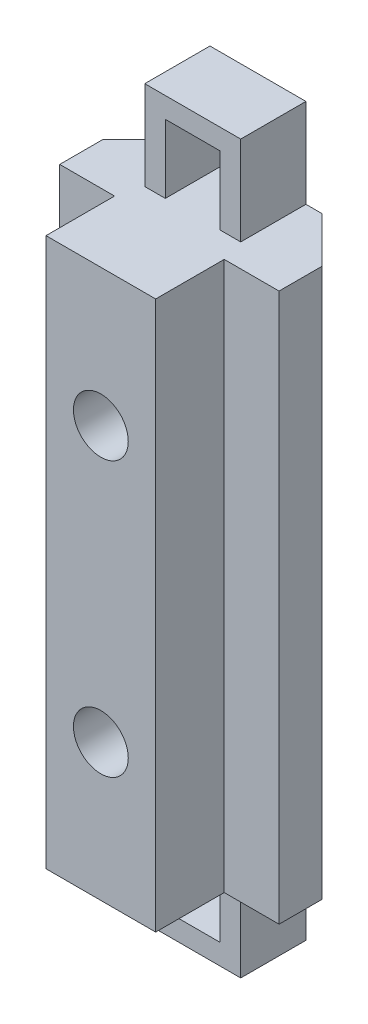
SolidWorks part; units mm, degrees
ref_plane "Front Plane" through (0, 0, 0) normal (0, 0, 1) x (1, 0, 0)
ref_plane "Top Plane" through (0, 0, 0) normal (0, 1, 0) x (1, 0, 0)
ref_plane "Right Plane" through (0, 0, 0) normal (1, 0, 0) x (0, 0, -1)
sketch "Sketch1" plane through (0, 0, 0) normal (0, 1, 0) x (1, 0, 0)
  line L0 (-4.2479, 4.7026) -> (8.7521, 4.7026)
  line L1 (8.7521, 4.7026) -> (8.7521, 1.7026)
  line L2 (-4.2479, 4.7026) -> (-4.2479, 1.7026)
  line L3 (-4.2479, 1.7026) -> (-2.5453, 0)
  line L4 (-44.2539, 0) -> (44.2539, 0) construction
  line L5 (8.7521, 1.7026) -> (7.0495, 0)
  line L6 (-2.5453, 0) -> (7.0495, 0)
  dimension "D1" = 13
  dimension "D2" = 3
  dimension "D3" = 3
extrude "Boss-Extrude1" add sketch "Sketch1" along normal blind 40
sketch "Sketch2" plane through (0, 0, 0) normal (0, 0, 1) x (1, 0, 0)
  line L0 (-2.5453, 40) -> (7.0495, 40) construction
  line L1 (2.2521, 40) -> (5.7521, 40)
  line L2 (2.2521, 40) -> (2.2521, 0)
  line L3 (2.2521, 0) -> (5.7521, 0)
  line L4 (5.7521, 40) -> (5.7521, 0)
  line L5 (55, 0) -> (-55, 0) construction
  line L7 (2.2521, 40) -> (-1.2479, 40)
  line L8 (2.2521, 40) -> (2.2521, 0)
  line L9 (2.2521, 0) -> (-1.2479, 0)
  line L10 (-1.2479, 40) -> (-1.2479, 0)
  line M9 (-2.5453, 0) -> (7.0495, 0)
  line M11 (7.0495, 40) -> (-2.5453, 40)
  dimension "D1" = 3.5
  dimension "D2" = 3.5
extrude "Boss-Extrude2" add sketch "Sketch2" along normal blind 5 contours L4 L2 M11 M9 | L10 L2 M11 M9 region at (4.0021, 20, 0) region at (0.5021, 20, 0)
sketch "Sketch4" plane through (0, 0, 5) normal (0, 0, 1) x (1, 0, 0)
  line L0 (2.2521, 40) -> (2.2521, 30)
  line L1 (5.7521, 40) -> (-1.2479, 40) construction
  line L2 (2.2521, 0) -> (2.2521, 10)
  line L3 (55, 0) -> (-55, 0) construction
  circle A0 centre (2.2521, 30) radius 2
  circle A1 centre (2.2521, 10) radius 2
  dimension "D3" = 4
  dimension "D4" = 4
  dimension "D1" = 10
  dimension "D2" = 10
extrude "Cut-Extrude1" cut sketch "Sketch4" against normal blind 7 contours A0 | A1 region at (0.8779, 28.6258, 5) region at (3.6263, 8.6258, 5)
sketch "Sketch5" plane through (0, 0, -4.7026) normal (0, 0, -1) x (-1, 0, 0)
  line L0 (-2.2521, 40) -> (-2.2521, 30)
  line L1 (-8.7521, 40) -> (4.2479, 40) construction
  line L2 (-2.2521, 0) -> (-2.2521, 10)
  line L3 (55, 0) -> (-55, 0) construction
  circle A0 centre (-2.2521, 30) radius 3.5
  circle A1 centre (-2.2521, 10) radius 3.5
  dimension "D3" = 7
  dimension "D4" = 7
  dimension "D1" = 10
  dimension "D2" = 10
extrude "Cut-Extrude2" cut sketch "Sketch5" against normal blind 3 draft 27 contours A0 | A1 region at (4.657, 27.5951, -4.7026) region at (-0.1528, 7.5951, -4.7026)
sketch "Sketch7" plane through (0, 0, -4.7026) normal (0, 0, -1) x (-1, 0, 0)
  line L0 (-8.7521, 0) -> (4.2479, 0) construction
  line L1 (-5.7521, 6.5) -> (1.2479, 6.5)
  line L2 (-5.7521, 6.5) -> (-5.7521, -6.5)
  line L3 (-5.7521, -6.5) -> (1.2479, -6.5)
  line L4 (1.2479, 6.5) -> (1.2479, -6.5)
  line L5 (-5.7521, 6.5) -> (1.2479, -6.5) construction
  line L6 (-5.7521, -6.5) -> (1.2479, 6.5) construction
  line L7 (-2.2521, 0) -> (-0.2521, 0)
  line L12 (-0.2521, 0) -> (-0.2521, -5)
  line L13 (-0.2521, -5) -> (-4.2521, -5)
  line L14 (-4.2521, -5) -> (-4.2521, 0)
  line L15 (-8.7521, 40) -> (4.2479, 40) construction
  line L16 (-5.7521, 46.5) -> (1.2479, 46.5)
  line L17 (-5.7521, 46.5) -> (-5.7521, 33.5)
  line L18 (-5.7521, 33.5) -> (1.2479, 33.5)
  line L19 (1.2479, 46.5) -> (1.2479, 33.5)
  line L20 (-5.7521, 46.5) -> (1.2479, 33.5) construction
  line L21 (-5.7521, 33.5) -> (1.2479, 46.5) construction
  line L22 (-4.2521, 0) -> (-0.2521, 0)
  line L23 (-0.2521, 40) -> (-0.2521, 45)
  line L24 (-0.2521, 45) -> (-0.2521, 43.2752)
  line L25 (-0.2521, 45) -> (-4.2521, 45)
  line L26 (-4.2521, 45) -> (-4.2521, 40)
  line L27 (-4.2521, 40) -> (-0.2521, 40)
  point P0 (-2.2521, 0)
  point P7 (-2.2521, 0)
  point P14 (-2.2521, 40)
  line M15 (-8.7521, 0) -> (4.2479, 0)
  line M17 (4.2479, 40) -> (-8.7521, 40)
  dimension "D1" = 13
  dimension "D2" = 7
  dimension "D3" = 2
  dimension "D4" = 5
  dimension "D5" = 13
  dimension "D6" = 7
  dimension "D7" = 4
  dimension "D8" = 5
  dimension "D9" = 4
extrude "Boss-Extrude3" add sketch "Sketch7" against normal blind 3 contours L26 L25 L23 L19 L16 L17 M17 | L13 L14 L2 L3 L4 L12 M15 region at (5.0021, -0.0955, -4.7026) region at (2.2521, 46.4045, -4.7026)
sketch "Sketch9" plane through (0, 0, -4.7026) normal (0, 0, -1) x (-1, 0, 0)
  line L0 (55, 0) -> (-55, 0) construction
  line L1 (-8.7521, 40) -> (4.2479, 40)
  line L2 (-8.7521, 40) -> (-8.7521, 0)
  line L3 (-8.7521, 0) -> (4.2479, 0)
  line L4 (4.2479, 40) -> (4.2479, 0)
  line L5 (4.2479, 40) -> (4.2479, 0) construction
extrude "Cut-Extrude4" cut sketch "Sketch9" against normal up to surface (4.7026 mm away) up to face at (6.4008, 20, 0)
sketch "Sketch10" plane through (0, 0, 0) normal (0, 0, -1) x (-1, 0, 0)
  line L0 (-5.7521, 40) -> (1.2479, 0) construction
  line L2 (-9.7521, 40) -> (5.2479, 40)
  line L3 (-9.7521, 40) -> (-9.7521, 0)
  line L4 (-9.7521, 0) -> (5.2479, 0)
  line L5 (5.2479, 40) -> (5.2479, 0)
  line L6 (-9.7521, 40) -> (5.2479, 0) construction
  line L7 (-9.7521, 0) -> (5.2479, 40) construction
  point P4 (-2.2521, 20)
  dimension "D1" = 15
extrude "Boss-Extrude4" add sketch "Sketch10" along normal blind 2.5
sketch "Sketch11" plane through (0, 0, 0) normal (0, 1, 0) x (1, 0, 0)
  line L0 (-5.2479, 2.5) -> (9.7521, 2.5)
  line L1 (9.7521, 2.5) -> (6.9237, 5.3284)
  line L2 (6.9237, 5.3284) -> (-5.2479, 5.3284)
  line L3 (-5.2479, 2.5) -> (-2.4195, 5.3284)
  line M1 (4.2521, 2.5) -> (5.7521, 2.5)
  line M2 (5.7521, 2.5) -> (5.7521, 4.7026)
  line M3 (5.7521, 4.7026) -> (4.2521, 4.7026)
  line M4 (4.2521, 4.7026) -> (4.2521, 2.5)
extrude "Boss-Extrude7" add sketch "Sketch11" along normal up to surface (40 mm away) contours M4 M1 M2 M3 | L3 L0 L1 L2 M4 M3 M2 region at (1.9602, 0, -3.8263) region at (5.0021, 0, -3.6013) up to face at (-0.4979, 40, -3.6013)
sketch "Sketch12" plane through (0, 0, -4.7026) normal (0, 0, -1) x (-1, 0, 0)
  line L0 (55, 0) -> (-55, 0) construction
  line L1 (-5.7521, -6.5) -> (1.2479, -6.5)
  line L2 (-5.7521, -6.5) -> (-5.7521, 0)
  line L3 (-5.7521, 0) -> (1.2479, 0)
  line L4 (1.2479, -6.5) -> (1.2479, 0)
  line L5 (1.2479, 0) -> (1.2479, -6.5) construction
  line L6 (-0.2521, 0) -> (-0.2521, -5) construction
  line L7 (-4.2521, -5) -> (-0.2521, -5)
  line L8 (-4.2521, -5) -> (-4.2521, 0)
  line L9 (-4.2521, 0) -> (-0.2521, 0)
  line L10 (-0.2521, -5) -> (-0.2521, 0)
  line L11 (-6.9237, 40) -> (2.4195, 40) construction
  line L12 (-5.7521, 46.5) -> (1.2479, 46.5)
  line L13 (-5.7521, 46.5) -> (-5.7521, 40)
  line L14 (-5.7521, 40) -> (1.2479, 40)
  line L15 (1.2479, 46.5) -> (1.2479, 40)
  line L16 (1.2479, 46.5) -> (1.2479, 40) construction
  line L17 (-4.2521, 45) -> (-4.2521, 40) construction
  line L18 (-4.2521, 45) -> (-0.2521, 45)
  line L19 (-4.2521, 45) -> (-4.2521, 40)
  line L20 (-4.2521, 40) -> (-0.2521, 40)
  line L21 (-0.2521, 45) -> (-0.2521, 40)
  line M1 (1.2479, -6.5) -> (1.2479, 0)
  line M2 (1.2479, 0) -> (-0.2521, 0)
  line M3 (-0.2521, 0) -> (-0.2521, -5)
  line M4 (-0.2521, -5) -> (-4.2521, -5)
  line M5 (-4.2521, -5) -> (-4.2521, 0)
  line M6 (-4.2521, 0) -> (-5.7521, 0)
  line M7 (-5.7521, 0) -> (-5.7521, -6.5)
  line M8 (-5.7521, -6.5) -> (1.2479, -6.5)
extrude "Boss-Extrude8" add sketch "Sketch12" along normal up to surface (0.6258 mm away) contours L18 L21 L14 L15 L12 L13 L19 | M8 M1 M2 M3 M4 M5 M6 M7 region at (5.6566, -3.25, -4.7026) region at (2.2521, 46.4045, -4.7026) up to face at (2.2521, 20, -5.3284)
sketch "Sketch13" plane through (0, 0, 0) normal (0, 0, 1) x (1, 0, 0)
  circle A0 centre (2.2521, 30) radius 2
  circle A1 centre (2.2521, 10) radius 2
extrude "Cut-Extrude5" cut sketch "Sketch13" against normal blind 10
sketch "Sketch14" plane through (9.7521, 0, 0) normal (1, 0, 0) x (0, 0, -1)
  line L1 (2.5, 40) -> (0, 40)
  line L2 (2.5, 40) -> (2.5, 0)
  line L3 (2.5, 0) -> (0, 0)
  line L4 (0, 40) -> (0, 0)
extrude "Boss-Extrude9" add sketch "Sketch14" along normal blind 0.5
sketch "Sketch15" plane through (-5.2479, 0, 0) normal (-1, 0, 0) x (0, 0, 1)
  line L1 (-2.5, 40) -> (0, 40)
  line L2 (-2.5, 40) -> (-2.5, 0)
  line L3 (-2.5, 0) -> (0, 0)
  line L4 (0, 40) -> (0, 0)
extrude "Boss-Extrude10" add sketch "Sketch15" along normal blind 0.5
sketch "Sketch16" plane through (0, 0, 0) normal (0, -1, 0) x (1, 0, 0)
  line L0 (-3.1851, -4.5628) -> (-3.7508, -5.1285)
  line L1 (-5.2479, -2.5) -> (-2.4195, -5.3284) construction
  line L2 (-4.5147, -3.2332) -> (-5.0804, -3.7989)
  line L3 (9.0189, -3.2332) -> (9.5846, -3.7989)
  line L4 (9.7521, -2.5) -> (6.9237, -5.3284) construction
  line L5 (7.5623, -4.6898) -> (8.128, -5.2555)
  line L6 (0.657, -5.3284) -> (0.657, -6.1284)
  line L7 (-1.2479, -5.3284) -> (5.7521, -5.3284) construction
  line L8 (0.657, -6.1284) -> (0.657, -6.3714)
  line L9 (9.5846, -3.7989) -> (6.6029, -6.7806)
  line L10 (9.5846, -3.7989) -> (11.5999, -1.7836)
  line L11 (10.2521, -2.5) -> (10.2521, -3.1314)
  line L12 (10.2521, -2.5) -> (9.7521, -2.5)
  line L13 (9.7521, -2.5) -> (6.9237, -5.3284)
  line L14 (6.9237, -5.3284) -> (-2.4195, -5.3284)
  line L15 (-2.4195, -5.3284) -> (-5.2479, -2.5)
  line L16 (-5.2479, -2.5) -> (-5.7479, -2.5)
  line L17 (-3.7508, -5.1285) -> (-6.826, -2.0532)
  line L18 (-5.7479, -2.5) -> (-5.7479, -3.1314)
  line L19 (-3.7508, -5.1285) -> (-2.4195, -6.4598)
  line L20 (-2.4195, -6.4598) -> (6.9237, -6.4598)
  line M3 (6.9237, -5.3284) -> (9.7521, -2.5)
  line M4 (9.7521, -2.5) -> (10.2521, -2.5)
  line M12 (-5.7479, -2.5) -> (-5.2479, -2.5)
  line M13 (-5.2479, -2.5) -> (-2.4195, -5.3284)
  dimension "D1" = 0.8
  dimension "D2" = 0.8
  dimension "D3" = 0.8
  dimension "D4" = 0.8
  dimension "D5" = 0.8
extrude "Boss-Extrude11" add sketch "Sketch16" against normal up to surface (40 mm away) contours L11 L3 L10 M4 M3 | L9 L3 L5 M3 | L19 L20 L9 L5 L14 L0 | L17 L0 L2 M13 | L18 L17 L2 M12 M13 region at (2.1886, 0, -5.8151) region at (-4.1327, 0, -4.1808) region at (-5.2163, 0, -3.0863) region at (8.5734, 0, -4.2444) region at (9.7205, 0, -3.0863) up to face at (2.2521, 40, -1.939)
sketch "Sketch17" plane through (0, 0, -5.3284) normal (0, 0, -1) x (-1, 0, 0)
  line L0 (-4.2521, 40) -> (-4.2521, 45) construction
  line L1 (-5.7521, 46.5) -> (1.2479, 46.5)
  line L2 (-5.7521, 46.5) -> (-5.7521, 40)
  line L3 (-5.7521, 40) -> (1.2479, 40)
  line L4 (1.2479, 46.5) -> (1.2479, 40)
  line L5 (-4.2521, 44.9531) -> (-0.2521, 44.9531)
  line L6 (-4.2521, 44.9531) -> (-4.2521, 40)
  line L7 (-4.2521, 40) -> (-0.2521, 40)
  line L8 (-0.2521, 44.9531) -> (-0.2521, 40)
  line L9 (-0.2521, 40) -> (-0.2521, 45) construction
  line L10 (1.2479, -6.5) -> (-5.7521, -6.5) construction
  line L11 (-5.7521, -6.5) -> (1.2479, -6.5)
  line L12 (-5.7521, -6.5) -> (-5.7521, 0)
  line L13 (-5.7521, 0) -> (1.2479, 0)
  line L14 (1.2479, -6.5) -> (1.2479, 0)
  line L15 (55, 0) -> (-55, 0) construction
  line L16 (1.2479, 0) -> (1.2479, -6.5) construction
  line L18 (-4.2521, -5) -> (0, -5)
  line L19 (-4.2521, -5) -> (-4.2521, 0)
  line L20 (-4.2521, 0) -> (0, 0)
  line L21 (0, -5) -> (0, 0)
  line M1 (1.2479, -6.5) -> (1.2479, 0)
  line M2 (1.2479, 0) -> (-0.2521, 0)
  line M4 (-0.2521, -5) -> (-4.2521, -5)
  line M5 (-4.2521, -5) -> (-4.2521, 0)
  line M6 (-4.2521, 0) -> (-5.7521, 0)
  line M7 (-5.7521, 0) -> (-5.7521, -6.5)
  line M8 (-5.7521, -6.5) -> (1.2479, -6.5)
extrude "Boss-Extrude12" add sketch "Sketch17" along normal up to surface (1.1314 mm away) contours L21 L18 M4 M5 M6 M7 M8 M1 M2 | L5 L8 L3 L4 L1 L2 L6 region at (2.2521, 46.4045, -5.3284) region at (5.6566, -3.25, -5.3284) up to face at (2.2521, 20, -6.4598)
sketch "Sketch18" plane through (0, 0, -5.3284) normal (0, 0, 1) x (1, 0, 0)
  circle A0 centre (2.2521, 30) radius 2
  circle A1 centre (2.2521, 10) radius 2
extrude "Cut-Extrude6" cut sketch "Sketch18" against normal blind 10
sketch "Sketch19" plane through (0, 0, -6.4598) normal (0, 0, -1) x (-1, 0, 0)
  circle A0 centre (-2.2521, 30) radius 2
  circle A1 centre (-2.2521, 10) radius 2
  circle A2 centre (-2.2521, 30) radius 3
  circle A3 centre (-2.2521, 10) radius 3
  dimension "D1" = 6
  dimension "D2" = 6
extrude "Cut-Extrude7" cut sketch "Sketch19" against normal blind 3 draft 19 contours A2 | A3
sketch "Sketch20" plane through (-1.2479, 0, 0) normal (-1, 0, 0) x (0, 0, 1)
  line L1 (5, 40) -> (0, 40)
  line L2 (5, 40) -> (5, 0)
  line L3 (5, 0) -> (0, 0)
  line L4 (0, 40) -> (0, 0)
extrude "Boss-Extrude13" add sketch "Sketch20" along normal blind 0.5
sketch "Sketch21" plane through (5.7521, 0, 0) normal (1, 0, 0) x (0, 0, -1)
  line L1 (-5, 40) -> (0, 40)
  line L2 (-5, 40) -> (-5, 0)
  line L3 (-5, 0) -> (0, 0)
  line L4 (0, 40) -> (0, 0)
extrude "Boss-Extrude14" add sketch "Sketch21" along normal blind 0.5
